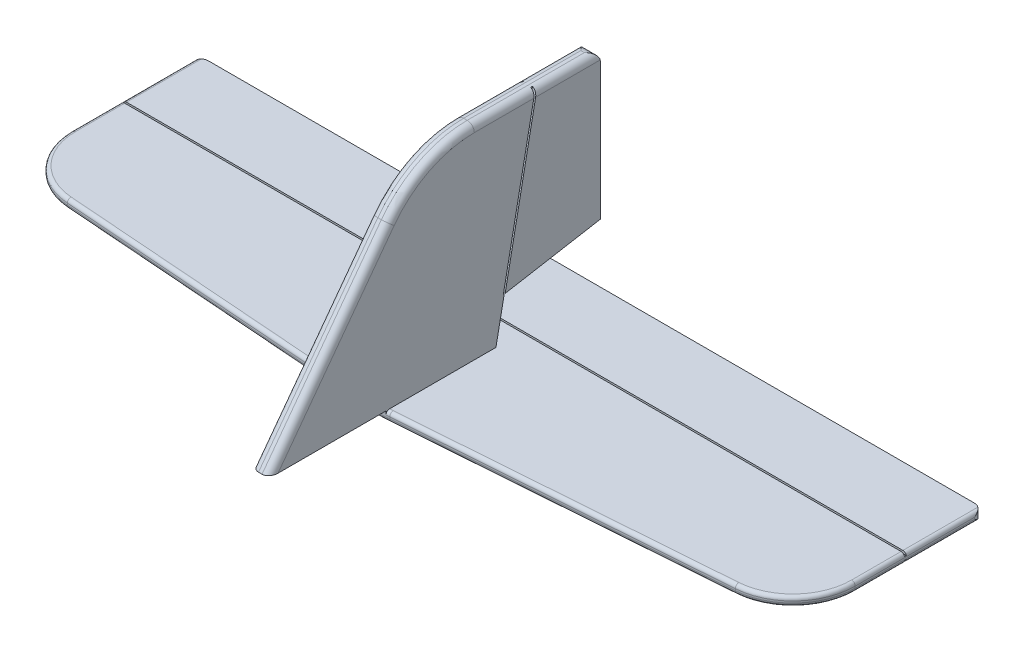
SolidWorks part; units mm, degrees
note: The reader was unsure of these and kept them because the rebuilt part matched: shared geometry of "Sketch4<3>".
ref_plane "Front Plane" through (0, 0, 0) normal (0, 0, 1) x (1, 0, 0)
ref_plane "Top Plane" through (0, 0, 0) normal (0, 1, 0) x (1, 0, 0)
ref_plane "Right Plane" through (0, 0, 0) normal (1, 0, 0) x (0, 0, -1)
sketch "Sketch1" plane through (0, 0, 0) normal (1, 0, 0) x (0, 0, -1)
  line L0 (0, 0) -> (-186, 0)
  line L1 (-186, 0) -> (-118.9916, 90.2879)
  line L2 (-70.811, 114.53) -> (-5, 114.53)
  line L3 (0, 109.53) -> (0, 0)
  line L4 (-36.0806, 114.53) -> (-58.6466, 0)
  line L5 (-54.0013, 23.5763) -> (0, 33.0385)
  arc A0 (-118.9916, 90.2879) -> (-70.811, 114.53) centre (-70.811, 54.53) cw
  arc A1 (-5, 114.53) -> (0, 109.53) centre (-5, 109.53) cw
  point P7 (-101, 114.53)
  point P10 (0, 114.53)
  point P15 (-58.6466, 0)
  dimension "D4" = 60
  dimension "D5" = 5
  dimension "D1" = 114.53
  dimension "D2" = 186
  dimension "D3" = 101
extrude "Boss-Extrude1" add sketch "Sketch1" along normal mid plane 10 contours A0 L1 L0 L4 L2 | A1 L2 L4 L5 L3
sketch "Sketch3" plane through (5, 0, 0) normal (1, 0, 0) x (0, 0, -1)
  line L0 (-54.0013, 23.5763) -> (-36.0806, 114.53)
  line L1 (-70.811, 114.53) -> (-5, 114.53) construction
  line L2 (-35.571, 114.53) -> (-53.4735, 23.6688)
  line L3 (-54.0013, 23.5763) -> (0, 33.0385) construction
  line L4 (-54.0013, 23.5763) -> (-58.6466, 0) construction
  line L5 (-36.5806, 114.53) -> (-54.5013, 23.5763)
  line L6 (-54.5013, 23.5763) -> (-54.0013, 23.5763)
  line L7 (-36.5806, 114.53) -> (-36.0806, 114.53)
  line L8 (-36.0806, 114.53) -> (-35.571, 114.53)
  line L9 (-54.0013, 23.5763) -> (-53.4735, 23.6688)
  line M7 (-54.0013, 23.5763) -> (0, 33.0385)
  line M10 (-5, 114.53) -> (-70.811, 114.53)
  dimension "D1" = 0.5
extrude "Cut-Extrude1" cut sketch "Sketch3" against normal blind 2.5 contours L2 L0 M10 M7 | L5 L6 L0 M10
mirror "Mirror1" about plane through (0, 0, 0) normal (1, 0, 0) of "Cut-Extrude1"
fillet "Fillet1" radius 4 6 edges at (-5, 114.53, 53.6958) (5, 114.53, 53.6958) (-5, 108.1279, 97.7788) (5, 108.1279, 97.7788) (-5, 45.144, 152.4958) (5, 45.144, 152.4958)
sketch "Sketch4" plane through (0, 0, 0) normal (0, 1, 0) x (1, 0, 0)
  line L0 (0, 0) -> (0, -120.787)
  line L6 (-215, 0) -> (215, 0)
  line L7 (220, -5) -> (220, -71.8683)
  line L8 (187.6076, -106.771) -> (0, -120.787)
  line L9 (-187.6076, -106.771) -> (0, -120.787)
  line L10 (-220, -5) -> (-220, -71.8683)
  line L11 (-220, -43.6125) -> (220, -43.6125)
  line L12 (-220, -44.1125) -> (220, -44.1125)
  line L13 (-220, -43.1125) -> (220, -43.1125)
  line L14 (220, -43.1125) -> (220, -44.1125)
  line L15 (-220, -43.1125) -> (-220, -44.1125)
  arc A4 (220, -71.8683) -> (187.6076, -106.771) centre (185, -71.8683) cw
  arc A5 (215, 0) -> (220, -5) centre (215, -5) cw
  arc A6 (-220, -71.8683) -> (-187.6076, -106.771) centre (-185, -71.8683) ccw
  arc A7 (-215, 0) -> (-220, -5) centre (-215, -5) ccw
  point P9 (220, 0)
  dimension "D2" = 220
  dimension "D3" = 5
  dimension "D1" = 35
  dimension "D4" = 0.5
extrude "Boss-Extrude2" add sketch "Sketch4" against normal blind 5 contours L10 A6 L9 L0 L12 | L10 L12 L0 L11 | L13 L10 L11 L0 | L6 A7 L10 L13 L0 | A4 L7 L12 L0 L8 | L0 L12 L7 L11 | L13 L0 L11 L7 | A5 L6 L0 L13 L7
fillet "Fillet2" radius 94 1 edges at (0, -2.5, 120.787)
extrude "Cut-Extrude2" cut sketch "Sketch4<3>" against normal blind 1.5 contours L13 L0 L11 L7 | L0 L12 L7 L11 | L10 L12 L0 L11 | L13 L10 L11 L0
sketch "Sketch4<3>" plane through (0, 0, 0) normal (0, 1, 0) x (1, 0, 0) same geometry as "Sketch4"
ref_plane "Plane1" through (0, -2.5, 0) normal (0, 1, 0) x (1, 0, 0)
mirror "Mirror2" about plane through (0, -2.5, 0) normal (0, 1, 0) of "Cut-Extrude2"
fillet "Fillet3" radius 2 15 edges at (220, 0, 57.9904) (210.6541, 0, 95.6773) (210.6541, -5, 95.6773) (6.0019, 0, 120.3332) (-220, -5, 57.9904) (-210.6541, 0, 95.6773) (-210.6541, -5, 95.6773) (220, -5, 57.9904) (97.3053, 0, 113.5174) (97.3053, -5, 113.5174) (0, -5, 120.525) (-220, 0, 57.9904) (-6.0019, 0, 120.3332) (-97.3053, -5, 113.5174) (-97.3053, 0, 113.5174)
